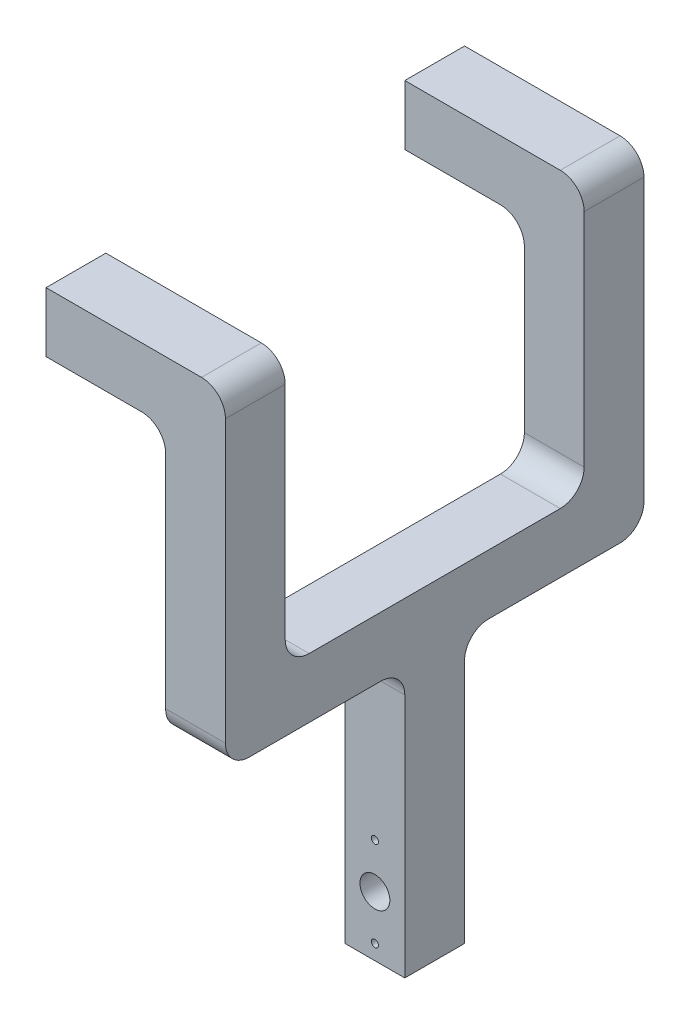
SolidWorks part; units mm, degrees
other "Marquage1"
sketch "Esquisse8" plane through (14, 100, 40) normal (0.0145, 0.0452, 0.9989) x (0.9993, 0.0332, -0.016)
ref_plane "Plan de face" through (0, 0, 0) normal (0, 0, 1) x (1, 0, 0)
ref_plane "Plan de dessus" through (0, 0, 0) normal (0, 1, 0) x (1, 0, 0)
ref_plane "Plan de droite" through (0, 0, 0) normal (1, 0, 0) x (0, 0, -1)
sketch "Esquisse1" plane through (0, 0, 0) normal (0, 0, 1) x (1, 0, 0)
  line L0 (9, 0) -> (9, 10) construction
  line L1 (0, 0) -> (18, 0) construction
  line L2 (0, 0) -> (0, 55) construction
  line L3 (0, 55) -> (18, 55) construction
  line L4 (18, 0) -> (18, 55) construction
  line L5 (9, 10) -> (0, 10) construction
  line L6 (9, 10) -> (9, 17.5) construction
  line L7 (4, 55) -> (14, 55)
  line L8 (4, 55) -> (4, 0)
  line L10 (14, 55) -> (14, 0)
  line L11 (4, 0) -> (14, 0)
  circle A1 centre (9, 10) radius 2.5
  circle A2 centre (9, 17.5) radius 0.5
  circle A4 centre (9, 2.5) radius 0.5
  circle A6 centre (16.5, 10) radius 0.5 [skipped]
  circle A7 centre (1.5, 10) radius 0.5 [skipped]
  point P24 (9, 10)
  dimension "D7" = 5
  dimension "D9" = 1
  dimension "D1" = 18
  dimension "D2" = 55
  dimension "D3" = 10
  dimension "D5" = 10
  dimension "D6" = 4
  dimension "D8" = 7.5
  dimension "D4" = 7.5
  dimension "D10" = 4
extrude "Boss.-Extru.1" add sketch "Esquisse1" along normal blind 10
sketch "Esquisse4" plane through (14, 0, 0) normal (1, 0, 0) x (0, 0, -1)
  line L0 (-30, 55) -> (20, 55)
  line L1 (20, 100) -> (30, 100)
  line L2 (30, 100) -> (30, 45)
  line L3 (30, 45) -> (-40, 45)
  line L4 (-40, 45) -> (-40, 100)
  line L5 (-40, 100) -> (-30, 100)
  line L6 (-30, 100) -> (-30, 55)
  line L8 (20, 55) -> (20, 100)
  line L9 (-5, 55) -> (-5, 0) construction
  line L10 (-10, 55) -> (0, 55) construction
  line L11 (-10, 0) -> (0, 0) construction
  point P5 (-5, 55)
  point P15 (-5, 45)
  dimension "D1" = 70
  dimension "D2" = 10
  dimension "D3" = 10
  dimension "D4" = 100
  dimension "D5" = 100
extrude "Boss.-Extru.2" add sketch "Esquisse4" against normal blind 10
sketch "Esquisse5" plane through (4, 0, 0) normal (-1, 0, 0) x (0, 0, 1)
  line L0 (-20, 100) -> (-20, 55) construction
  line L1 (-30, 100) -> (-20, 100)
  line L2 (-30, 100) -> (-30, 90)
  line L3 (-30, 90) -> (-20, 90)
  line L4 (-20, 100) -> (-20, 90)
  line L5 (40, 100) -> (40, 45) construction
  line L6 (30, 100) -> (40, 100)
  line L7 (30, 100) -> (30, 90)
  line L8 (30, 90) -> (40, 90)
  line L9 (40, 100) -> (40, 90)
  dimension "D1" = 10
extrude "Boss.-Extru.3" add sketch "Esquisse5" along normal blind 20
fillet "Congé1" radius 4 10 edges at (9, 55, -20) (9, 55, 30) (4, 90, -25) (4, 90, 35) (9, 45, -30) (9, 45, 40) (14, 100, -25) (14, 100, 35) (9, 45, 0) (9, 45, 10)
hole_wizard "Dégagement M11" positions "Esquisse6" profile "Esquisse7" hole size "M1" standard "ISO" end condition through all
sketch "Esquisse6" plane through (0, 0, 10) normal (0, 0, 1) x (1, 0, 0)
  point P0 (9, 17.5)
  point P3 (9, 2.5)
sketch "Esquisse7" plane through (9, 17.5, 10) normal (1, 0, 0) x (0, -1, 0)
  line L0 (0, 0) -> (0, 40)
  line L1 (0, 40) -> (0.6, 40)
  line L2 (0.6, 40) -> (0.6, 0)
  line L5 (0.6, 0) -> (0, 0)
  line L11 (0, -6.35) -> (0, 107.95) construction
  dimension "Diamètre du perçage jusqu'au prochain" = 1.2
  dimension "Profondeur du perçage jusqu'au prochain" = 40
sketch "Esquisse9" plane through (14, 0, 0) normal (1, 0, 0) x (0, 0, -1)
  line L5 (0, 0) -> (-2.5, 0)
  line L6 (0, 0) -> (0, 20)
  line L7 (0, 20) -> (-2.5, 20)
  line L8 (-2.5, 0) -> (-2.5, 20)
  dimension "D2" = 20
  dimension "D4" = 2.5
extrude "Enlèv. mat.-Extru.1" [suppressed] cut sketch "Esquisse9" against normal up to surface (10 mm away) up to face at (4, 51.6857, 5)
equation "\"D3@Esquisse1\"=10"
equation "\"D6@Esquisse1\"=(\"D1@Esquisse1\"-\"D5@Esquisse1\")/2"
equation "\"D8@Esquisse1\"=15/2"
